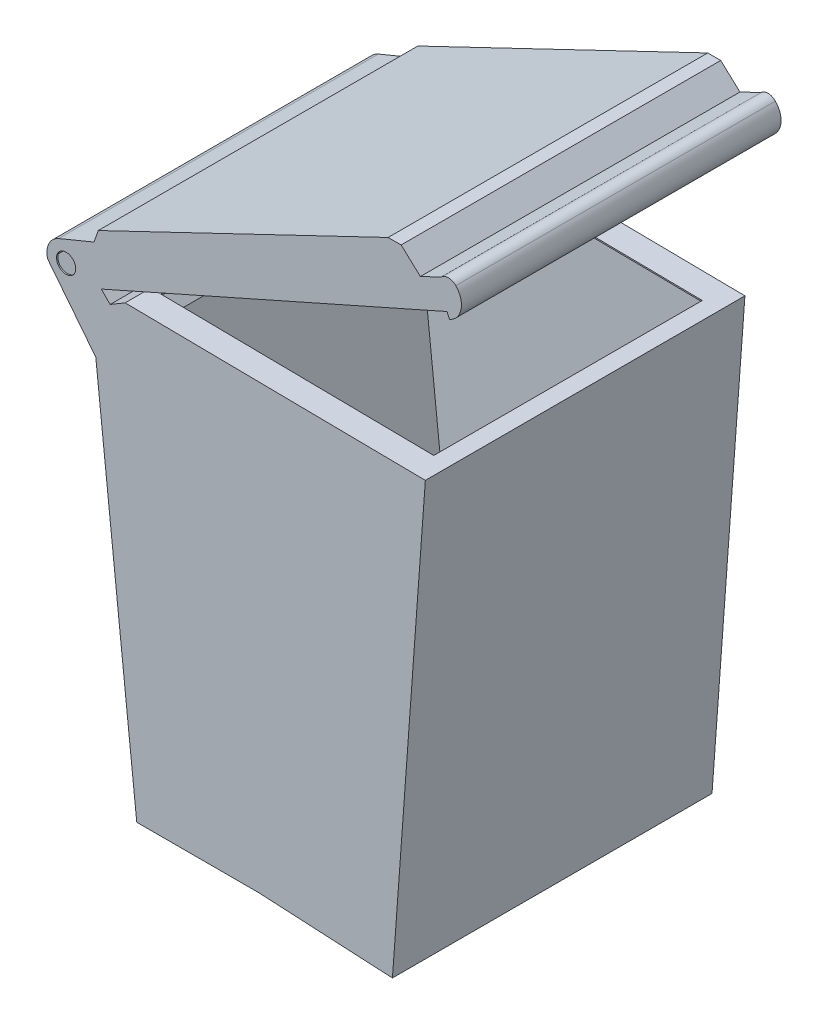
SolidWorks part; units mm, degrees
ref_plane "Front Plane" through (0, 0, 0) normal (0, 0, 1) x (1, 0, 0)
ref_plane "Top Plane" through (0, 0, 0) normal (0, 1, 0) x (1, 0, 0)
ref_plane "Right Plane" through (0, 0, 0) normal (1, 0, 0) x (0, 0, -1)
sketch "Sketch1" plane through (0, 0, 0) normal (0, 0, 1) x (1, 0, 0)
  line L0 (2.6475, 7.9425) -> (13.2376, 7.9425) construction
  line L1 (7.716, 1.8333) -> (10.3754, 1.6938)
  line L2 (10.3754, 1.6938) -> (11.0292, 10.5838)
  line L3 (11.0292, 10.5838) -> (5.0647, 10.6561)
  line L4 (5.0647, 10.6561) -> (4.7672, 10.4793)
  line L5 (4.7672, 10.4793) -> (4.5904, 10.6561)
  line L6 (4.5904, 10.6561) -> (11.4601, 13.7044)
  line L7 (11.4601, 13.7044) -> (11.5093, 13.5933)
  line L8 (11.3472, 14.2414) -> (10.9312, 14.042)
  line L9 (10.9312, 14.042) -> (10.5482, 14.3938)
  line L10 (10.5482, 14.3938) -> (10.2903, 14.3938)
  line L11 (10.2903, 14.3938) -> (4.5306, 11.6334)
  line L12 (4.5306, 11.6334) -> (4.446, 11.393)
  line L13 (4.446, 11.393) -> (3.7457, 11.1025)
  line L14 (3.5279, 10.637) -> (4.4814, 9.4295)
  line L15 (4.4814, 9.4295) -> (5.2954, 1.8333)
  line L16 (5.2954, 1.8333) -> (7.716, 1.8333)
  arc A0 (11.5093, 13.5933) -> (11.6349, 14.2362) centre (11.3472, 13.9587) ccw
  arc A1 (11.6349, 14.2362) -> (11.3472, 14.2414) centre (11.4885, 14.0949) ccw
  arc A2 (3.7457, 11.1025) -> (3.5279, 10.637) centre (3.8917, 10.7505) ccw
  dimension "D2" = 5.08
  dimension "D1" = 12.7
  dimension "D3" = 8.89
extrude "Boss-Extrude1" add sketch "Sketch1" along normal blind 6.35
shell "Shell1" thickness 0.0254
sketch "Sketch3" plane through (0.13, 10.716, 0) normal (0.0121, 0.9999, 0) x (0.9999, -0.0121, 0)
  line L0 (5.1415, -0.508) -> (10.56, -0.508)
  line L5 (10.56, -0.508) -> (10.56, -5.842)
  line L6 (10.56, -5.842) -> (5.1415, -5.842)
  line L7 (5.1415, -5.842) -> (5.1415, -0.508)
  line L11 (10.1149, -6.35) -> (4.3891, -6.35) construction
  line L12 (10.1149, 0) -> (4.3891, 0) construction
  dimension "D3" = 0.508
  dimension "D4" = 0.508
extrude "Cut-Extrude2" cut sketch "Sketch3" against normal blind 1.524
sketch "Sketch4" plane through (0, 0, 6.35) normal (0, 0, 1) x (1, 0, 0)
  circle A0 centre (3.8917, 10.7505) radius 0.1905
  dimension "D1" = 0.381
extrude "Cut-Extrude3" cut sketch "Sketch4" against normal through all
